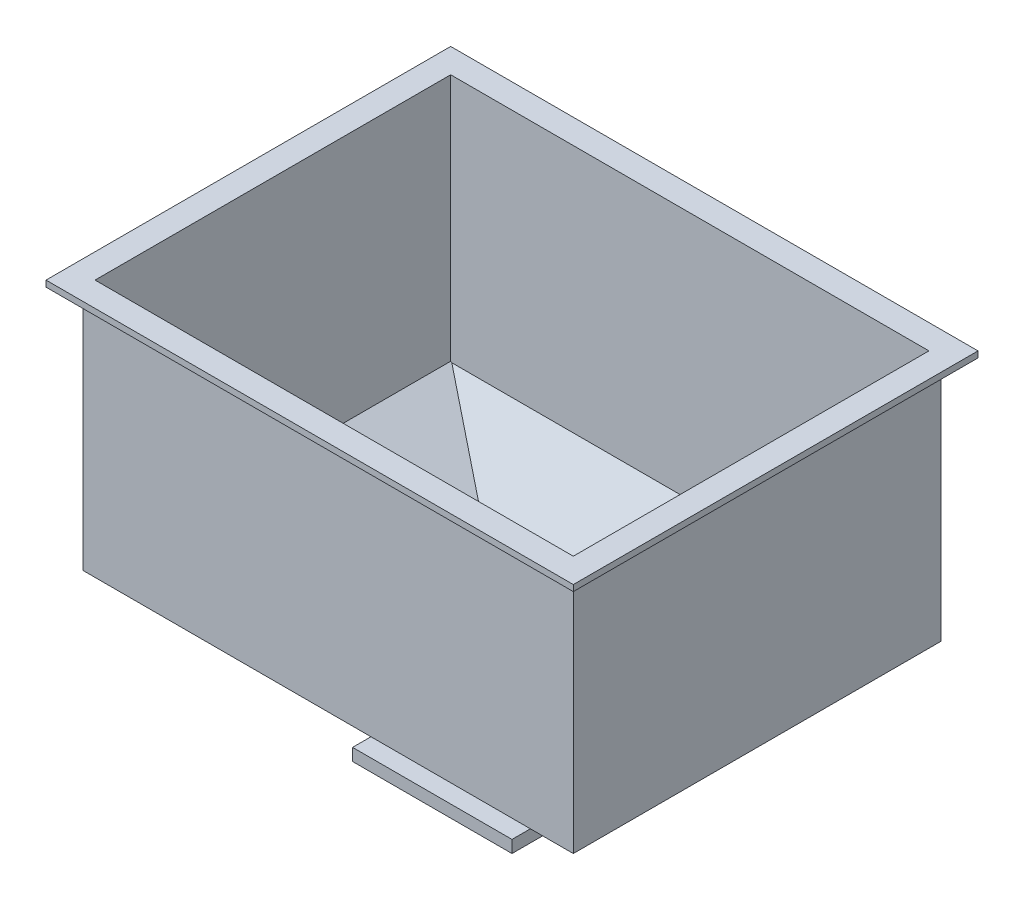
SolidWorks part; units mm, degrees
ref_plane "Front Plane" through (0, 0, 0) normal (0, 0, 1) x (1, 0, 0)
ref_plane "Top Plane" through (0, 0, 0) normal (0, 1, 0) x (1, 0, 0)
ref_plane "Right Plane" through (0, 0, 0) normal (1, 0, 0) x (0, 0, -1)
sketch "Sketch1" plane through (0, 0, 0) normal (0, 0, 1) x (1, 0, 0)
  line L0 (-200, -100) -> (-50, -200)
  line L1 (-200, 100) -> (200, 100)
  line L2 (-200, 100) -> (-200, -100)
  line L3 (-200, -100) -> (200, -100)
  line L4 (200, 100) -> (200, -100)
  line L5 (-50, -200) -> (50, -200)
  line L6 (50, -200) -> (200, -100)
  point P6 (0, -200)
  point P7 (0, -100)
  point P14 (200, 0)
  point P15 (0, 100)
  dimension "D1" = 200
  dimension "D2" = 400
  dimension "D3" = 100
  dimension "D4" = 100
extrude "Boss-Extrude1" add sketch "Sketch1" against normal blind 300 contours L4 L1 L2 L3 | L5 L6 L3 L0 region at (0, -140, 0) region at (0, 0, 0)
sketch "Sketch2" plane through (0, 0, 0) normal (1, 0, 0) x (0, 0, -1)
  line L0 (0, -100) -> (100, -200)
  line L1 (300, -200) -> (0, -200) construction
  line L2 (100, -200) -> (0, -200)
  line L3 (0, -200) -> (0, -100)
  line L4 (300, -100) -> (300, -200)
  line L5 (300, -200) -> (300, -100) construction
  line L6 (300, -200) -> (200, -200)
  line L7 (200, -200) -> (300, -100)
  dimension "D1" = 100
  dimension "D2" = 100
  dimension "D3" = 100
extrude "Cut-Extrude1" cut sketch "Sketch2" against normal through all both and the other way through all
shell "Shell1" thickness 5 removed face at (0, -200, -150) removed face at (0, 100, -150)
ref_plane "Plane1" through (0, 100, 0) normal (0, 1, 0) x (1, 0, 0)
sketch "Sketch3" plane through (0, 100, 0) normal (0, 1, 0) x (1, 0, 0)
  line L0 (-200, 0) -> (200, 0) construction
  line L1 (-215, 315) -> (215, 315)
  line L2 (-215, 315) -> (-215, -15)
  line L3 (-215, -15) -> (215, -15)
  line L4 (215, 315) -> (215, -15)
  line L5 (200, 300) -> (200, 0) construction
  point P6 (0, 0)
  point P7 (0, -15)
  point P8 (215, 150)
  point P11 (200, 150)
  dimension "D1" = 330
  dimension "D2" = 430
extrude "Boss-Extrude2" add sketch "Sketch3" along normal blind 5
shell "Shell2" thickness 5 removed face at (0, 100, -150) removed face at (0, 105, -150)
ref_plane "Plane5" through (0, -200, 0) normal (0, -1, 0) x (-1, 0, 0)
sketch "Sketch5" plane through (0, -200, 0) normal (0, -1, 0) x (1, 0, 0)
  line L0 (-50, -200) -> (-50, -100) construction
  line L1 (65, -215) -> (-65, -215)
  line L2 (65, -215) -> (65, -85)
  line L3 (65, -85) -> (-65, -85)
  line L4 (-65, -215) -> (-65, -85)
  line L8 (-50, -200) -> (50, -200) construction
  point P4 (-50, -150)
  point P7 (-65, -150)
  point P10 (0, -215)
  point P13 (0, -200)
  dimension "D1" = 130
  dimension "D2" = 130
extrude "Boss-Extrude3" add sketch "Sketch5" along normal blind 10
sketch "Sketch6" plane through (0, -210, 0) normal (0, -1, 0) x (1, 0, 0)
  line L0 (65, -85) -> (-65, -85) construction
  line L1 (-65, -85) -> (-65, -215) construction
  circle A0 centre (0, -150) radius 9
  circle A1 centre (0, -150) radius 12
  point P5 (0, -85)
  point P8 (-65, -150)
  dimension "D1" = 18
  dimension "D2" = 3
extrude "Boss-Extrude4" [suppressed] add sketch "Sketch6" along normal blind 30
